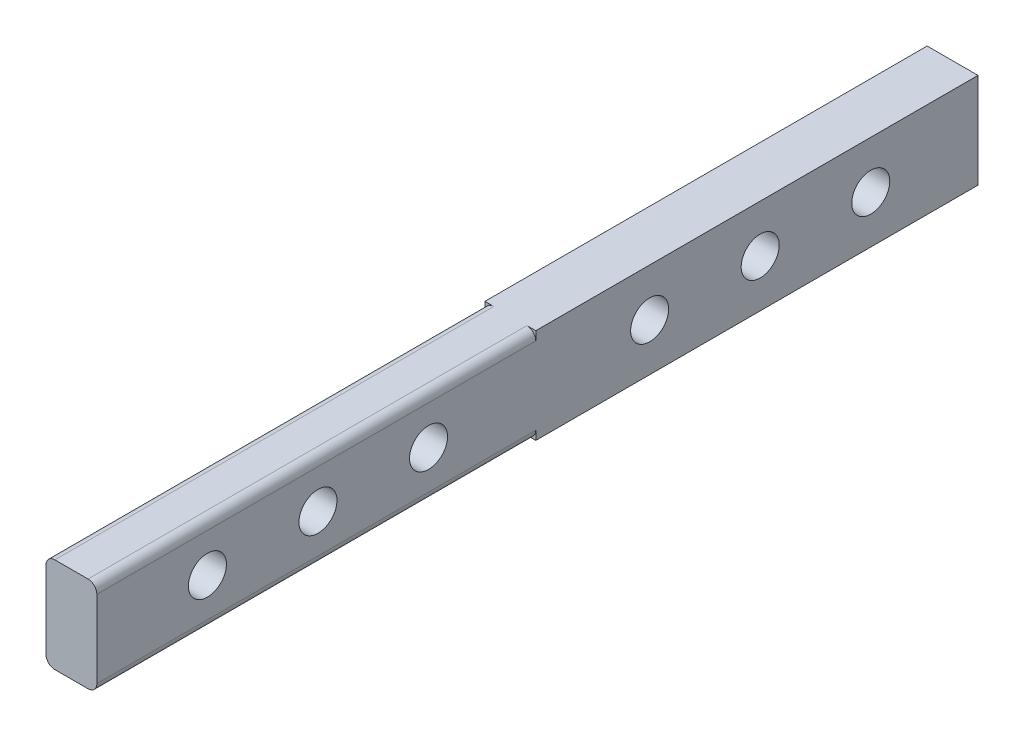
SolidWorks part; units mm, degrees
ref_plane "前视基准面" through (0, 0, 0) normal (0, 0, 1) x (1, 0, 0)
ref_plane "上视基准面" through (0, 0, 0) normal (0, 1, 0) x (1, 0, 0)
ref_plane "右视基准面" through (0, 0, 0) normal (1, 0, 0) x (0, 0, -1)
other "Configuration Table"
sketch "草图1" plane through (0, 0, 0) normal (0, 0, 1) x (1, 0, 0)
  line L1 (-2.875, 5.375) -> (2.875, 5.375)
  line L2 (-2.875, 5.375) -> (-2.875, -5.375)
  line L3 (-2.875, -5.375) -> (2.875, -5.375)
  line L4 (2.875, 5.375) -> (2.875, -5.375)
  line L5 (0, -5.375) -> (0, 5.375) construction
  line L6 (-2.875, 0) -> (2.875, 0) construction
  point P0 (0, 0)
  dimension "D1" = 10.75
  dimension "D2" = 5.75
extrude "凸台-拉伸1" add sketch "草图1" along normal blind 49.6264
fillet "圆角1" radius 1 4 edges at (2.875, -5.375, 24.8132) (-2.875, -5.375, 24.8132) (-2.875, 5.375, 24.8132) (2.875, 5.375, 24.8132)
extrude "凸台-拉伸2" add sketch "草图1<2>" against normal blind 50
sketch "草图1<2>" plane through (0, 0, 0) normal (0, 0, 1) x (1, 0, 0) same geometry as "草图1"
sketch "草图2" plane through (2.875, 0, 0) normal (1, 0, 0) x (0, 0, -1)
  line L0 (-49.6264, 0) -> (50, 0) construction
  line L1 (-49.6264, -4.375) -> (-49.6264, 4.375) construction
  line L2 (50, -5.375) -> (50, 5.375) construction
  line L3 (-37.1264, 0) -> (-24.6264, 0) construction
  circle A0 centre (-37.1264, 0) radius 2.15
  circle A1 centre (-24.6264, 0) radius 2.15
  circle A2 centre (-12.1264, 0) radius 2.15
  circle A3 centre (0.3736, 0) radius 2.15 [skipped]
  circle A4 centre (12.8736, 0) radius 2.15
  circle A5 centre (25.3736, 0) radius 2.15
  circle A6 centre (37.8736, 0) radius 2.15
  dimension "D1" = 4.3
  dimension "D2" = 12.5
  dimension "D4" = 12.5
  dimension "D3" = 7
extrude "切除-拉伸1" cut sketch "草图2" against normal through all
